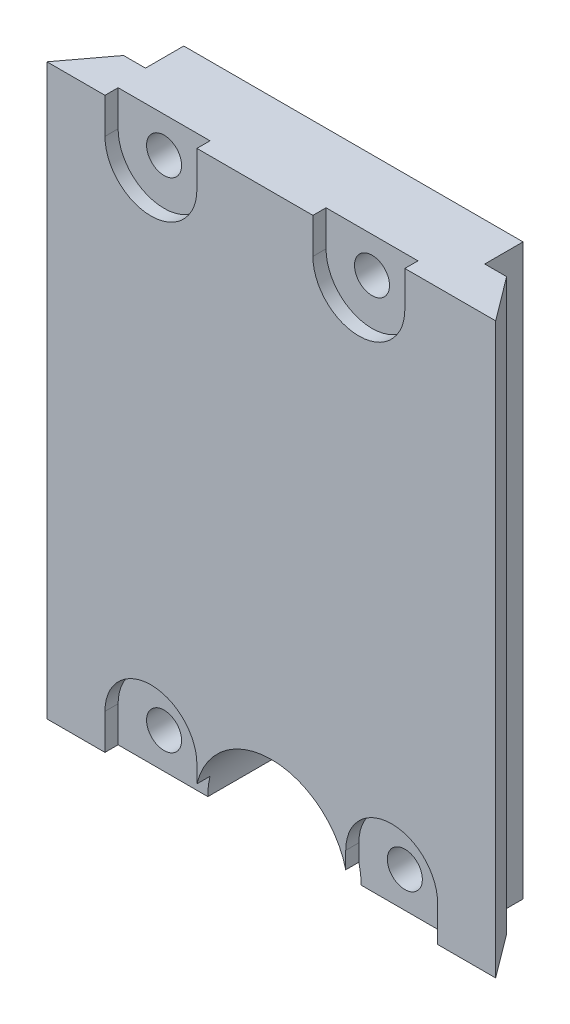
SolidWorks part; units mm, degrees
ref_plane "前视基准面" through (0, 0, 0) normal (0, 0, 1) x (1, 0, 0)
ref_plane "上视基准面" through (0, 0, 0) normal (0, 1, 0) x (1, 0, 0)
ref_plane "右视基准面" through (0, 0, 0) normal (1, 0, 0) x (0, 0, -1)
other "Configuration Table"
sketch "草图2" plane through (0, 0, 0) normal (0, 1, 0) x (1, 0, 0)
  line L0 (0, 0) -> (41, 0)
  line L1 (41, 0) -> (38, 4)
  line L2 (38, 4) -> (3, 4)
  line L3 (3, 4) -> (0, 0)
  line L4 (20.5, 4) -> (20.5, 0) construction
  dimension "D1" = 4
  dimension "D2" = 41
  dimension "D3" = 35
extrude "凸台-拉伸1" add sketch "草图2" along normal blind 52
sketch "草图3" plane through (0, 0, -4) normal (0, 0, -1) x (-1, 0, 0)
  line L0 (-38, 52) -> (-3, 52) construction
  line L1 (-36, 52) -> (-5, 52)
  line L2 (-36, 52) -> (-36, 0)
  line L3 (-36, 0) -> (-5, 0)
  line L4 (-5, 52) -> (-5, 0)
  line L5 (-36, 52) -> (-5, 0) construction
  line L6 (-36, 0) -> (-5, 52) construction
  line L7 (-38, 0) -> (-3, 0) construction
  line L8 (-38, 52) -> (-38, 0) construction
  line L9 (-3, 52) -> (-3, 0) construction
  point P4 (-20.5, 26)
  dimension "D1" = 2
  dimension "D2" = 2
extrude "凸台-拉伸2" add sketch "草图3" along normal blind 3.5
sketch "草图4" plane through (0, 0, 0) normal (0, 0, 1) x (1, 0, 0)
  line L0 (20.5, 52) -> (20.5, 0) construction
  line L1 (0, 52) -> (41, 52) construction
  line L2 (0, 0) -> (41, 0) construction
  line L3 (0, 26) -> (41, 26) construction
  line L4 (0, 52) -> (0, 0) construction
  line L5 (41, 52) -> (41, 0) construction
  line L6 (9.5, 3.25) -> (9.5, 48.75) construction
  line L7 (9.5, 48.75) -> (28.5, 48.75) construction
  circle A0 centre (9.5, 3.25) radius 1.6
  circle A1 centre (31.5, 3.25) radius 1.6
  circle A4 centre (9.5, 48.75) radius 1.6
  circle A5 centre (28.5, 48.75) radius 1.6
  dimension "D1" = 3.2
  dimension "D4" = 3
  dimension "D2" = 22.75
  dimension "D3" = 11
extrude "切除-拉伸1" cut sketch "草图4" against normal up to next
sketch "草图6" plane through (0, 0, 0) normal (0, 0, 1) x (1, 0, 0)
  circle A0 centre (20.5, 0.05) radius 7
  circle A1 centre (20.5, 0.05) radius 3.65 construction
  dimension "D1" = 14
extrude "切除-拉伸2" cut sketch "草图6" against normal through all
sketch "草图7" plane through (0, 0, 0) normal (0, 0, 1) x (1, 0, 0)
  circle A14 centre (9.5, 48.75) radius 4
  circle A15 centre (28.5, 48.75) radius 4
  circle A16 centre (9.5, 3.25) radius 4
  circle A17 centre (31.5, 3.25) radius 4
  dimension "D1" = 8
extrude "切除-拉伸3" cut sketch "草图7" against normal blind 1.2
sketch "草图8" plane through (0, 0, -1.2) normal (0, 0, 1) x (1, 0, 0)
  line L0 (9.5, 48.75) -> (9.5, 52) construction
  line L1 (11.8318, 52) -> (7.1682, 52) construction
  line L2 (5.3, 48.75) -> (5.3, 52)
  line L3 (13.7, 48.75) -> (13.7, 52)
  line L4 (28.5, 48.75) -> (28.5, 52) construction
  line L5 (30.8318, 52) -> (26.1682, 52) construction
  line L6 (24.3, 48.75) -> (24.3, 52)
  line L7 (32.7, 48.75) -> (32.7, 52)
  line L8 (9.5, 3.25) -> (9.5, 0) construction
  line L9 (11.8318, 0) -> (7.1682, 0) construction
  line L10 (13.7, 3.25) -> (13.7, 0)
  line L11 (5.3, 3.25) -> (5.3, 0)
  line L12 (31.5, 3.25) -> (31.5, 0) construction
  line L13 (33.8318, 0) -> (29.1682, 0) construction
  line L14 (35.7, 3.25) -> (35.7, 0)
  line L15 (27.3, 3.25) -> (27.3, 0)
  arc A0 (5.3, 48.75) -> (13.7, 48.75) centre (9.5, 48.75) ccw
  arc A1 (13.7, 52) -> (5.3, 52) centre (9.5, 52) ccw
  arc A2 (24.3, 48.75) -> (32.7, 48.75) centre (28.5, 48.75) ccw
  arc A3 (32.7, 52) -> (24.3, 52) centre (28.5, 52) ccw
  arc A4 (13.7, 3.25) -> (5.3, 3.25) centre (9.5, 3.25) ccw
  arc A5 (5.3, 0) -> (13.7, 0) centre (9.5, 0) ccw
  arc A6 (35.7, 3.25) -> (27.3, 3.25) centre (31.5, 3.25) ccw
  arc A7 (27.3, 0) -> (35.7, 0) centre (31.5, 0) ccw
  point P5 (9.5, 50.375)
  point P10 (28.5, 50.375)
  point P20 (9.5, 1.625)
  point P30 (31.5, 1.625)
  dimension "D1" = 4.2
extrude "切除-拉伸4" cut sketch "草图8" along normal up to next
